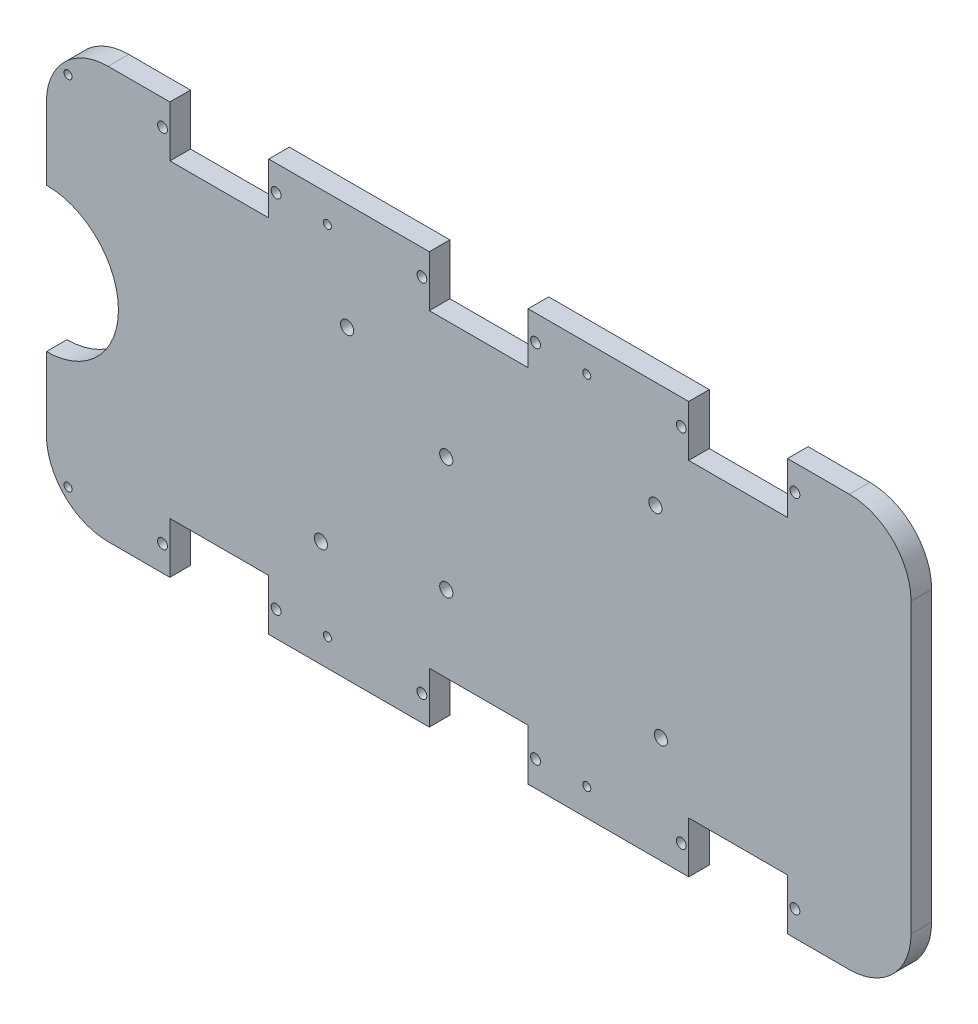
SolidWorks part; units mm, degrees
ref_plane "Front Plane" through (0, 0, 0) normal (0, 0, 1) x (1, 0, 0)
ref_plane "Top Plane" through (0, 0, 0) normal (0, 1, 0) x (1, 0, 0)
ref_plane "Right Plane" through (0, 0, 0) normal (1, 0, 0) x (0, 0, -1)
sketch "Sketch1" plane through (0, 0, 0) normal (0, 0, 1) x (1, 0, 0)
  line L1 (-90, -50) -> (90, -50)
  line L2 (-105, -35) -> (-105, 35)
  line L3 (-90, 50) -> (90, 50)
  line L4 (105, -35) -> (105, 35)
  line L5 (-105, -50) -> (105, 50) construction
  line L6 (-105, 50) -> (105, -50) construction
  arc A0 (-105, -35) -> (-90, -50) centre (-90, -35) ccw
  arc A1 (90, -50) -> (105, -35) centre (90, -35) ccw
  arc A2 (105, 35) -> (90, 50) centre (90, 35) ccw
  arc A3 (-90, 50) -> (-105, 35) centre (-90, 35) ccw
  point P0 (0, 0)
  dimension "D3" = 15
  dimension "D1" = 210
  dimension "D2" = 100
extrude "Boss-Extrude2" add sketch "Sketch1" along normal blind 5
sketch "Sketch2" plane through (0, 0, 5) normal (0, 0, 1) x (1, 0, 0)
  line L0 (-105, 0) -> (-75, 0) construction
  line L1 (-105, 35) -> (-105, -35) construction
  line L2 (-75, 0) -> (-51, 0) construction
  line L3 (-51, 0) -> (-12, 0) construction
  line L4 (-12, 0) -> (12, 0) construction
  line L5 (12, 0) -> (51, 0) construction
  line L6 (51, 0) -> (75, 0) construction
  line L7 (-75, 0) -> (-75, 50) construction
  line L8 (90, 50) -> (-90, 50) construction
  line L9 (-51, 0) -> (-51, 50) construction
  line L10 (-12, 0) -> (-12, 50) construction
  line L11 (12, 0) -> (12, 50) construction
  line L12 (51, 0) -> (51, 50) construction
  line L13 (75, 0) -> (75, 50) construction
  line L14 (-75, 0) -> (-75, -50) construction
  line L15 (-90, -50) -> (90, -50) construction
  line L16 (-51, 0) -> (-51, -50) construction
  line L17 (-12, 0) -> (-12, -50) construction
  line L18 (12, 0) -> (12, -50) construction
  line L19 (51, 0) -> (51, -50) construction
  line L20 (75, 0) -> (75, -50) construction
  line L21 (51, -37.6) -> (75, -37.6)
  line L22 (-75, 50) -> (-51, 50)
  line L23 (-75, 50) -> (-75, 37.6)
  line L24 (-75, 37.6) -> (-51, 37.6)
  line L25 (-51, 50) -> (-51, 37.6)
  line L26 (-12, 50) -> (12, 50)
  line L27 (-12, 50) -> (-12, 37.6)
  line L28 (-12, 37.6) -> (12, 37.6)
  line L29 (12, 50) -> (12, 37.6)
  line L30 (51, 50) -> (75, 50)
  line L31 (51, 50) -> (51, 37.6)
  line L32 (51, 37.6) -> (75, 37.6)
  line L33 (75, 50) -> (75, 37.6)
  line L34 (75, -50) -> (75, -37.6)
  line L35 (51, -50) -> (75, -50)
  line L36 (51, -50) -> (51, -37.6)
  line L37 (-12, -37.6) -> (12, -37.6)
  line L38 (12, -50) -> (12, -37.6)
  line L39 (-12, -50) -> (12, -50)
  line L40 (-12, -50) -> (-12, -37.6)
  line L41 (-75, -37.6) -> (-51, -37.6)
  line L42 (-51, -50) -> (-51, -37.6)
  line L43 (-75, -50) -> (-51, -50)
  line L44 (-75, -50) -> (-75, -37.6)
  dimension "D1" = 30
  dimension "D2" = 24
  dimension "D3" = 39
  dimension "D4" = 24
  dimension "D5" = 39
  dimension "D6" = 24
  dimension "D7" = 12.4
  dimension "D8" = 12.4
extrude "Cut-Extrude1" cut sketch "Sketch2" against normal blind 5
sketch "Sketch3" plane through (0, 0, 5) normal (0, 0, 1) x (1, 0, 0)
  line L0 (-51, 50) -> (-51, 37.6) construction
  line L1 (-105, 0) -> (105, 0) construction
  line L2 (-75, 50) -> (-75, 37.6) construction
  line L3 (-105, 35) -> (-105, -35) construction
  line L4 (-75, 43.8) -> (-76.8, 43.8) construction
  line L5 (-51, 43.8) -> (-49.2, 43.8) construction
  line L6 (105, -35) -> (105, 35) construction
  circle A0 centre (-76.8, 43.8) radius 1.2
  circle A1 centre (-49.2, 43.8) radius 1.2
  circle A2 centre (-13.8, 43.8) radius 1.2
  circle A3 centre (13.8, 43.8) radius 1.2
  circle A4 centre (49.2, 43.8) radius 1.2
  circle A5 centre (76.8, 43.8) radius 1.2
  circle A6 centre (-76.8, -43.8) radius 1.2
  circle A7 centre (-49.2, -43.8) radius 1.2
  circle A8 centre (-13.8, -43.8) radius 1.2
  circle A9 centre (13.8, -43.8) radius 1.2
  circle A10 centre (49.2, -43.8) radius 1.2
  circle A11 centre (76.8, -43.8) radius 1.2
  dimension "D2" = 1.8
  dimension "D3" = 3
  dimension "D1" = 1.8
extrude "Cut-Extrude2" cut sketch "Sketch3" against normal blind 5
sketch "Sketch5" plane through (0, 0, 5) normal (0, 0, 1) x (1, 0, 0)
  line L0 (-51, 50) -> (-51, 37.6) construction
  line L1 (105, 0) -> (-95.1885, 0) construction
  line L2 (-12, 50) -> (-51, 50) construction
  line L3 (-51, 37.6) -> (-51, 50) construction
  line L4 (-31.5, 50) -> (-36.75, 50) construction
  line L5 (-36.75, 50) -> (-36.75, 43.3602) construction
  circle A4 centre (-36.75, 43.3602) radius 0.975
  circle A5 centre (26.25, 43.3602) radius 0.975
  circle A6 centre (26.25, -43.3602) radius 0.975
  circle A7 centre (-36.75, -43.3602) radius 0.975
  circle A8 centre (-99.75, 43.3602) radius 0.975
  circle A9 centre (-99.75, -43.3602) radius 0.975
  point P13 (105, 0)
  dimension "D1" = 2
  dimension "D2" = 2
extrude "Cut-Extrude3" cut sketch "Sketch5" against normal blind 10
sketch "Sketch6" plane through (0, 0, 5) normal (0, 0, 1) x (1, 0, 0)
  line L0 (75, 37.6) -> (75, -37.6) construction
  line L1 (-105, 35) -> (-105, -35) construction
  circle A0 centre (-105, 0) radius 17.5
extrude "Cut-Extrude4" cut sketch "Sketch6" against normal blind 10
sketch "Sketch8" plane through (0, 0, 0) normal (0, 0, -1) x (-1, 0, 0)
  line L0 (-63, 37.6) -> (-63, 0) construction
  line L1 (-51, 37.6) -> (-75, 37.6) construction
  line L2 (-63, 0) -> (-8.65, 0) construction
  line L3 (-8.65, 0) -> (31.97, 0) construction
  line L4 (31.97, 0) -> (31.97, 24.11) construction
  line L5 (-8.65, 0) -> (-8.65, -24.11) construction
  line L6 (-8.65, 0) -> (-42.91, 0) construction
  line L7 (-8.65, -24.11) -> (38.33, -24.11) construction
  line L8 (-8.65, 0) -> (7.88, 0) construction
  line L9 (7.88, 0) -> (7.88, -19.03) construction
  line L10 (7.88, 0) -> (7.88, 8.88) construction
  line L11 (-42.91, 0) -> (-42.91, 24.11) construction
  line L12 (-8.65, -24.11) -> (-44.24, -24.11) construction
  circle A0 centre (31.97, 24.11) radius 1.6
  circle A3 centre (38.33, -24.11) radius 1.6
  circle A4 centre (7.88, 8.88) radius 1.6
  circle A5 centre (7.88, -19.03) radius 1.6
  circle A6 centre (-42.91, 24.11) radius 1.6
  circle A8 centre (-44.24, -24.11) radius 1.6
  dimension "D4" = 46.98
  dimension "D5" = 16.53
  dimension "D8" = 34.26
  dimension "D9" = 24.11
  dimension "D1" = 54.35
  dimension "D2" = 40.62
  dimension "D3" = 24.11
  dimension "D6" = 19.03
  dimension "D7" = 8.88
  dimension "D10" = 35.59
extrude "Cut-Extrude5" cut sketch "Sketch8" against normal blind 10
sketch "Sketch10" plane through (0, 0, 0) normal (0, 0, -1) x (-1, 0, 0)
  line L0 (71.2901, 0) -> (71.2901, -11.5)
  line L2 (76.2901, 0) -> (76.2901, -16.5)
  line L3 (65.0901, 11.5) -> (65.0901, 0) construction
  line L13 (53.8901, -16.5) -> (76.2901, -16.5)
  line L14 (53.8901, 16.5) -> (53.8901, -16.5)
  line L15 (87.5, 0) -> (71.2901, 0) construction
  line L16 (58.8901, 11.5) -> (71.2901, 11.5)
  line L17 (58.8901, 11.5) -> (58.8901, -11.5)
  line L18 (58.8901, -11.5) -> (71.2901, -11.5)
  line L20 (58.8901, 11.5) -> (71.2901, -11.5) construction
  line L21 (58.8901, -11.5) -> (71.2901, 11.5) construction
  line L24 (53.8901, 16.5) -> (71.2901, 16.5)
  line L25 (71.2901, 11.5) -> (71.2901, 16.5)
  line L26 (71.2901, 0) -> (76.2901, 0)
  line L27 (53.8901, 16.5) -> (76.2901, 16.5) construction
  line L28 (76.2901, 16.5) -> (76.2901, -16.5) construction
  line L29 (71.2901, 11.5) -> (71.2901, -11.5) construction
  arc A0 (105, 17.5) -> (105, -17.5) centre (105, 0) ccw construction
  dimension "D1" = 22.4099
  dimension "D2" = 23
  dimension "D3" = 12.4
  dimension "D4" = 5
extrude "Boss-Extrude3" add sketch "Sketch10" along normal blind 17.7 contours L18 L17 L16 region at (-73.7901, -0.3988, 0)
sketch "Sketch12" plane through (0, 0, -17.7) normal (0, 0, -1) x (-1, 0, 0)
  line L0 (58.8901, 0) -> (96.2, 0) construction
  line L1 (58.8901, 11.5) -> (58.8901, -11.5) construction
  line L3 (65.0901, 34.0148) -> (65.0901, -11.5) construction
  line L4 (58.8901, -11.5) -> (71.2901, -11.5) construction
  line L5 (65.0901, -11.5) -> (65.0901, -13.8) construction
  line L6 (58.8901, 0) -> (71.2901, 0) construction
  circle A0 centre (65.0901, -13.8) radius 1.2
  circle A1 centre (65.0901, 13.8) radius 1.2
  point P14 (0, 0)
  point P15 (0, 0)
  point P16 (0, 0)
  point P19 (0, 0)
  point P20 (0, 0)
  dimension "D1" = 2.3
extrude "Cut-Extrude6" cut sketch "Sketch12" against normal blind 5
